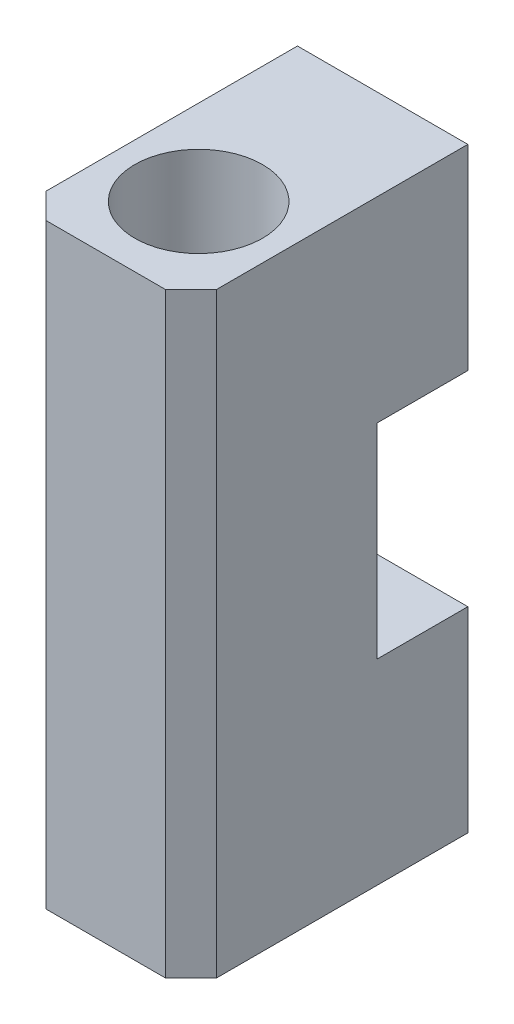
SolidWorks part; units mm, degrees
material "6061-T4 (SS)"
ref_plane "Piano frontale" through (0, 0, 0) normal (0, 0, 1) x (1, 0, 0)
ref_plane "Piano superiore" through (0, 0, 0) normal (0, 1, 0) x (1, 0, 0)
ref_plane "Piano destro" through (0, 0, 0) normal (1, 0, 0) x (0, 0, -1)
sketch "Schizzo1" plane through (0, 0, 0) normal (0, 0, 1) x (1, 0, 0)
  line L1 (0, 0) -> (20, 0)
  line L2 (0, 0) -> (0, 70)
  line L3 (0, 70) -> (20, 70)
  line L4 (20, 0) -> (20, 70)
  dimension "D1" = 70
  dimension "D2" = 20
extrude "Estrusione-Estrusione1" add sketch "Schizzo1" against normal blind 32.5
sketch "Schizzo2" plane through (0, 0, 0) normal (0, -1, 0) x (1, 0, 0)
  line L0 (10, 0) -> (10, -32.5) construction
  line L1 (0, 0) -> (20, 0) construction
  line L2 (0, -32.5) -> (20, -32.5) construction
  circle A0 centre (10, -10.9) radius 7.5
  point P6 (10, -10.9)
  dimension "D2" = 15
  dimension "D1" = 21.6
extrude "Taglio-Estrusione1" cut sketch "Schizzo2" against normal through all
sketch "Schizzo3" plane through (0, 0, -32.5) normal (0, 0, -1) x (-1, 0, 0)
  line L0 (0, 6) -> (-20, 6) construction
  line L1 (0, 70) -> (0, 0) construction
  line L2 (-20, 0) -> (-20, 70) construction
  line L3 (0, 35) -> (-20, 35) construction
  line L4 (0, 0) -> (-20, 0) construction
  line L5 (0, 64) -> (-20, 64) construction
  line L6 (-10, 0) -> (-10, 70) construction
  line L7 (-20, 70) -> (0, 70) construction
  point P16 (-10, 6)
  point P17 (-10, 64)
  dimension "D1" = 6
hole_wizard "Foro Ø4.0 (4)-1" positions "Schizzo3D1" profile "Schizzo4" hole size "Ø4.0" standard "ISO"
sketch3d "Schizzo3D1"
  point P0 (10, 6, -32.5)
  point P3 (10, 64, -32.5)
sketch "Schizzo4" plane through (10, 6, -32.5) normal (1, 0, 0) x (0, 1, 0)
  line L0 (0, 0) -> (0, 11.2017)
  line L1 (0, 11.2017) -> (2, 10)
  line L2 (2, 10) -> (2, 0)
  line L5 (2, 0) -> (0, 0)
  line L10 (0, 11.2017) -> (-2, 10) construction
  line L11 (0, -6.35) -> (0, 107.95) construction
  dimension "Hole Dia." = 4
  dimension "Hole Depth" = 10
  dimension "Drill Angle" = 118
ref_axis "Assi1" through (10, 70, -10.9) along (0, -1, 0)
chamfer "Smusso1" distance 3 angle 45 2 edges at (0, 35, 0) (20, 35, 0)
sketch "Schizzo7" plane through (0, 0, 0) normal (-1, 0, 0) x (0, 0, 1)
  line L0 (-32.5, 47) -> (-21.854, 47)
  line L1 (-32.5, 0) -> (-32.5, 70) construction
  line L2 (-32.5, 35) -> (0, 35) construction
  line L3 (0, 70) -> (0, 0) construction
  line L4 (-21.854, 47) -> (-21.854, 23)
  line L5 (-32.5, 47) -> (-32.5, 23)
  line L6 (-32.5, 23) -> (-21.854, 23)
  point P11 (-21.854, 35)
  dimension "D1" = 12
extrude "Taglio-Estrusione4" cut sketch "Schizzo7" against normal blind 26
